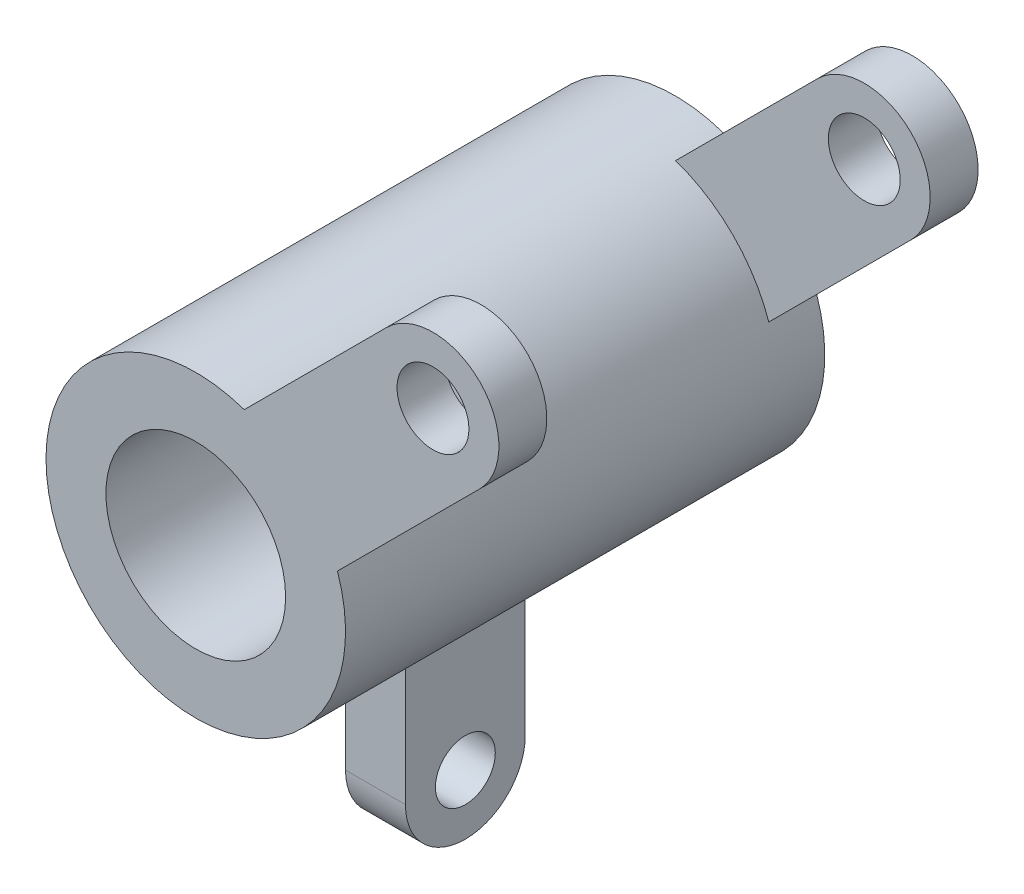
SolidWorks part; units mm, degrees
ref_plane "Спереди" through (0, 0, 0) normal (0, 0, 1) x (1, 0, 0)
ref_plane "Сверху" through (0, 0, 0) normal (0, 1, 0) x (1, 0, 0)
ref_plane "Справа" through (0, 0, 0) normal (1, 0, 0) x (0, 0, -1)
sketch "Эскиз1" plane through (0, 0, 0) normal (0, 0, 1) x (1, 0, 0)
  line L0 (0, 0) -> (19.799, 19.799) construction
  line L1 (-3.8891, 3.8891) -> (15.9099, 23.6881)
  line L2 (3.8891, -3.8891) -> (23.6881, 15.9099)
  line L3 (0, 0) -> (37.813, 0) construction
  circle A0 centre (0, 0) radius 7.5
  circle A1 centre (0, 0) radius 12.5
  arc A2 (-3.8891, 3.8891) -> (3.8891, -3.8891) centre (0, 0) ccw
  arc A3 (23.6881, 15.9099) -> (15.9099, 23.6881) centre (19.799, 19.799) ccw
  circle A4 centre (19.799, 19.799) radius 3
  point P4 (9.8995, 9.8995)
  dimension "D1" = 15
  dimension "D2" = 25
  dimension "D6" = 6
  dimension "D3" = 11
  dimension "D4" = 28
  dimension "D5" = 45
extrude "Бобышка-Вытянуть1" add sketch "Эскиз1" along normal blind 40 contours L1 A1 L2 A0 | L2 A1 L1 A0 region at (-5.5533, -5.5533, 0) region at (6.6396, 6.6396, 0)
extrude "Бобышка-Вытянуть3" add sketch "Эскиз1<4>" along normal blind 4 contours L2 A3 L1 A1 A4 region at (15.1299, 15.1299, 0)
sketch "Эскиз1<4>" plane through (0, 0, 0) normal (0, 0, 1) x (1, 0, 0) same geometry as "Эскиз1"
ref_plane "Плоскость1" through (0, 0, 20) normal (0, 0, 1) x (1, 0, 0)
mirror "Зеркальное отражение1" about plane through (0, 0, 20) normal (0, 0, 1) of "Бобышка-Вытянуть3"
sketch "Эскиз2" plane through (0, 0, 0) normal (1, 0, 0) x (0, 0, -1)
  line L0 (-40, 0) -> (0, 0) construction
  line L1 (-40, 12.5) -> (-40, -12.5) construction
  line L2 (-20, 0) -> (-20, -25) construction
  line L3 (-20, -25) -> (-20, -12.5) construction
  line L4 (-25, -25) -> (-25, -12.5)
  line L5 (-15, -25) -> (-15, -12.5)
  line L6 (-25, -12.5) -> (-25, -10.5)
  line L7 (-25, -10.5) -> (-15, -10.5)
  line L8 (-15, -10.5) -> (-15, -12.5)
  arc A0 (-25, -25) -> (-15, -25) centre (-20, -25) ccw
  arc A1 (-15, -12.5) -> (-25, -12.5) centre (-20, -12.5) ccw
  circle A2 centre (-20, -25) radius 2.5
  point P8 (-20, -18.75)
  dimension "D1" = 5
  dimension "D4" = 5
  dimension "D2" = 25
  dimension "D3" = 2
extrude "Бобышка-Вытянуть4" add sketch "Эскиз2" along normal blind 2.5 and the other way blind 2.5 contours L5 A1 L7 L4 A0 A2 region at (0, -19.1479, 20)
